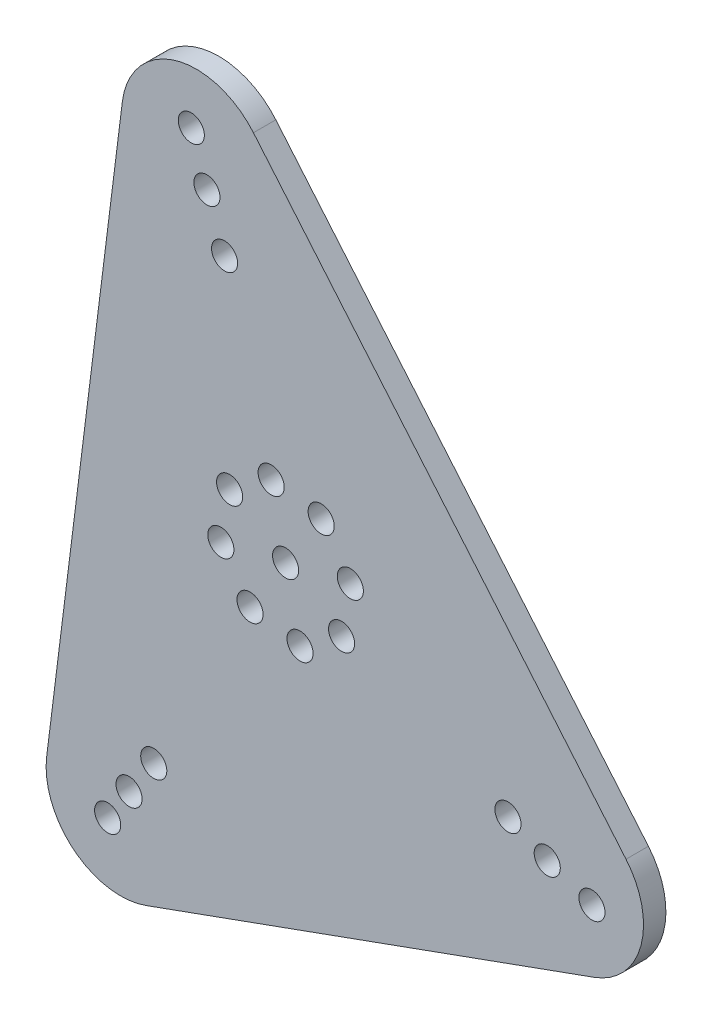
SolidWorks part; units mm, degrees
ref_plane "Front Plane" through (0, 0, 0) normal (0, 0, 1) x (1, 0, 0)
ref_plane "Top Plane" through (0, 0, 0) normal (0, 1, 0) x (1, 0, 0)
ref_plane "Right Plane" through (0, 0, 0) normal (1, 0, 0) x (0, 0, -1)
sketch "Sketch1" plane through (0, 0, 0) normal (0, 0, 1) x (1, 0, 0)
  line L35 (0.6673, 53.6405) -> (50.6108, -5.7241)
  line L36 (46.3562, -21.567) -> (-13.7286, -43.2725)
  line L37 (-27.0489, -32.6261) -> (-16.9075, 48.444)
  arc A0 (50.6108, -5.7241) -> (46.3562, -21.567) centre (42.9587, -12.1618) cw
  arc A1 (0.6673, 53.6405) -> (-16.9075, 48.444) centre (-6.9848, 47.2027) ccw
  arc A2 (-13.7286, -43.2725) -> (-27.0489, -32.6261) centre (-17.1262, -33.8674) cw
  point P84 (-14.0667, 58.8925)
  point P86 (52.1121, -14.5818)
  point P87 (-26.5404, -40.3775)
  point P88 (-15.4086, 71.1538)
  point P89 (59.8411, -16.6956)
  point P90 (-29.0741, -48.8161)
  dimension "D1" = 10
extrude "Boss-Extrude1" add sketch "Sketch1" along normal blind 3
sketch "Sketch2" plane through (0, 0, 0) normal (0, 0, -1) x (-1, 0, 0)
  circle A0 centre (7.6627, 50.0425) radius 1.75
  circle A1 centre (5.5682, 43.894) radius 1.75
  circle A2 centre (3.2034, 37.4078) radius 1.75
  circle A3 centre (-46.0452, -13.3188) radius 1.75
  circle A4 centre (-40.0492, -11.1647) radius 1.75
  circle A5 centre (-34.7866, -8.7214) radius 1.75
  circle A6 centre (18.8723, -35.6484) radius 1.75
  circle A7 centre (16.0084, -31.1736) radius 1.75
  circle A8 centre (12.697, -26.2512) radius 1.75
  point P2 (0, 0)
  point P5 (5.5682, 43.894)
  point P8 (3.2034, 37.4078)
  point P11 (-46.0452, -13.3188)
  point P14 (-40.0492, -11.1647)
  point P17 (-34.7866, -8.7214)
  point P20 (18.8723, -35.6484)
  point P23 (16.0084, -31.1736)
  point P26 (12.697, -26.2512)
  dimension "D1" = 3.5
extrude "Cut-Extrude1" cut sketch "Sketch2" against normal through all
sketch "Sketch3" plane through (0, 0, 0) normal (0, 0, -1) x (-1, 0, 0)
  circle A0 centre (-4.9771, 5.8556) radius 1.75
  dimension "D1" = 3.5
extrude "Cut-Extrude2" cut sketch "Sketch3" against normal through all
sketch "Sketch4" plane through (0, 0, 0) normal (0, 0, -1) x (-1, 0, 0)
  circle A0 centre (-3.0414, 14.5347) radius 1.75
  dimension "D1" = 3.5
extrude "Cut-Extrude3" cut sketch "Sketch4" against normal through all
pattern_circular "CirPattern1" count 8 every 45 about axis through (4.9771, 5.8556, 0) along (0, 0, -1) of "Cut-Extrude3"
